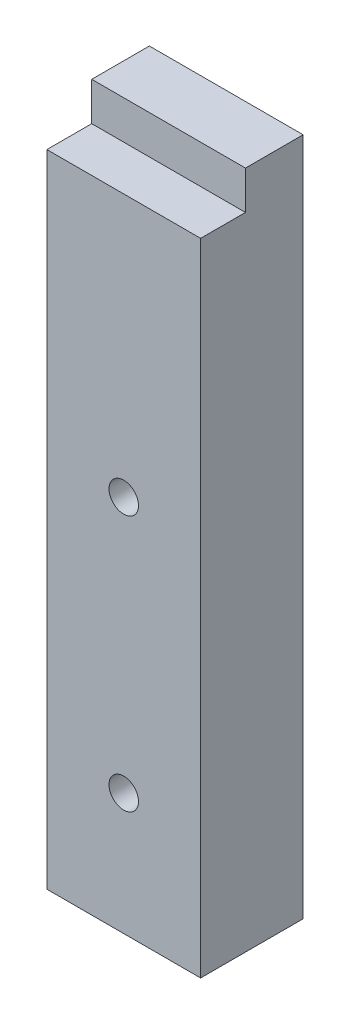
SolidWorks part; units mm, degrees
ref_plane "Płaszczyzna przednia" through (0, 0, 0) normal (0, 0, 1) x (1, 0, 0)
ref_plane "Płaszczyzna górna" through (0, 0, 0) normal (0, 1, 0) x (1, 0, 0)
ref_plane "Płaszczyzna prawa" through (0, 0, 0) normal (1, 0, 0) x (0, 0, -1)
sketch "Sketch1" plane through (0, 0, 0) normal (0, 0, 1) x (1, 0, 0)
  line L0 (6, 50) -> (6, 29.5) construction
  line L1 (0, 0) -> (12, 0)
  line L2 (0, 0) -> (0, 50)
  line L3 (0, 50) -> (12, 50)
  line L4 (12, 0) -> (12, 50)
  line L5 (6, 29.5) -> (6, 9.5) construction
  circle A0 centre (6, 29.5) radius 1.15
  circle A1 centre (6, 9.5) radius 1.15
  dimension "D3" = 2.3
  dimension "D1" = 50
  dimension "D2" = 12
  dimension "D4" = 20.5
  dimension "D5" = 40.5
extrude "Boss-Extrude1" add sketch "Sketch1" along normal blind 8
sketch "Sketch2" plane through (0, 50, 0) normal (0, 1, 0) x (1, 0, 0)
  line L0 (12, -8) -> (12, 0) construction
  line L1 (0, 0) -> (12, 0)
  line L2 (0, 0) -> (0, -4.5)
  line L3 (0, -4.5) -> (12, -4.5)
  line L4 (12, 0) -> (12, -4.5)
  line L5 (12, -8) -> (0, -8) construction
  dimension "D1" = 3.5
extrude "Boss-Extrude2" add sketch "Sketch2" along normal blind 3
